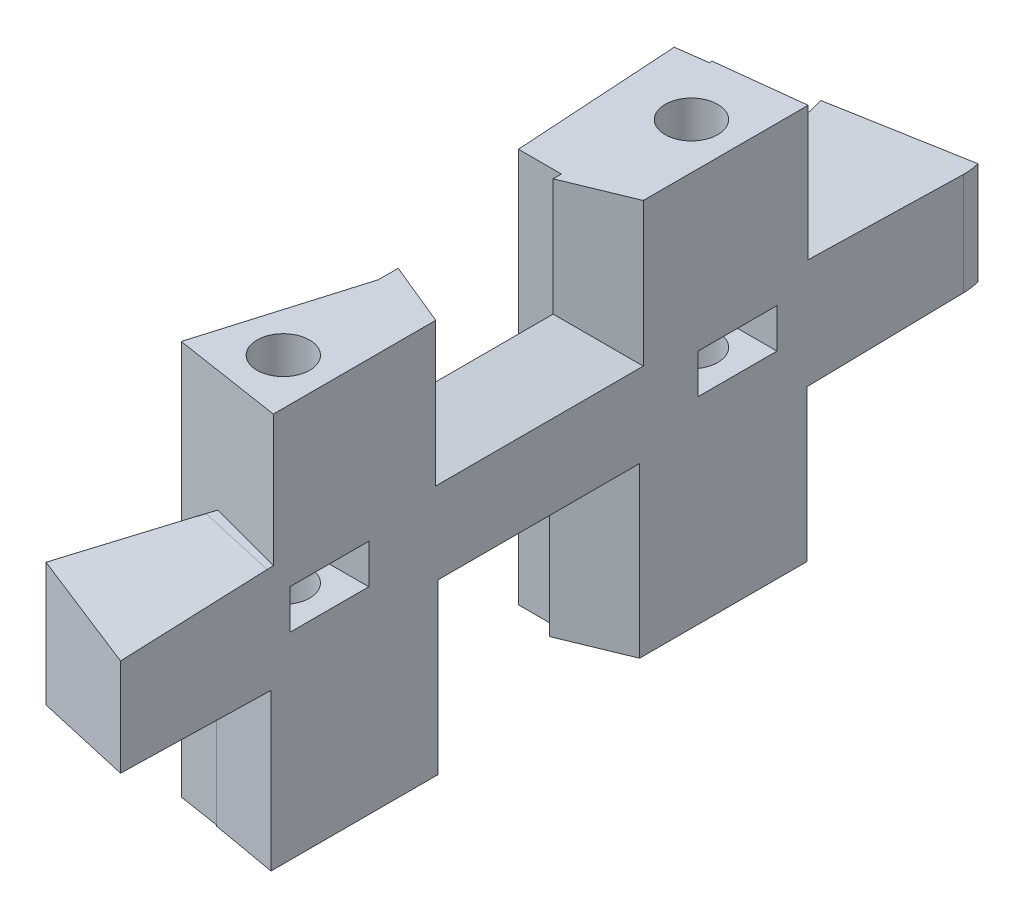
SolidWorks part; units mm, degrees
ref_plane "前视基准面" through (0, 0, 0) normal (0, 0, 1) x (1, 0, 0)
ref_plane "上视基准面" through (0, 0, 0) normal (0, 1, 0) x (1, 0, 0)
ref_plane "右视基准面" through (0, 0, 0) normal (1, 0, 0) x (0, 0, -1)
sketch "草图1" plane through (0, 0, 0) normal (0, 1, 0) x (1, 0, 0)
  line L0 (-7.1461, -29.9145) -> (11.328, -33.8659)
  line L1 (11.328, -33.8659) -> (15, -21.4825)
  line L2 (15, -21.4825) -> (3.725, -18.6661)
  line L3 (3.725, -18.6661) -> (7.1461, -7.129)
  line L4 (7.1461, -7.129) -> (15, -7.129)
  line L5 (15, -7.129) -> (15, 6.7954)
  line L6 (15, 6.7954) -> (3.8787, 6.7954)
  line L7 (3.8787, 6.7954) -> (3.0965, 19.265)
  line L8 (3.0965, 19.265) -> (14.551, 22.591)
  line L9 (14.551, 22.591) -> (11.328, 34.5234)
  line L10 (11.328, 34.5234) -> (-0.3541, 31.368)
  line L11 (-0.3541, 31.368) -> (-2.0104, 37.5)
  line L12 (-15, -37.5) -> (15, -37.5)
  line L13 (15, -37.5) -> (15, 37.5)
  line L14 (15, 37.5) -> (-15, 37.5)
  line L15 (-15, 37.5) -> (-15, -37.5)
sketch "草图2" plane through (0, 0, 0) normal (0, 1, 0) x (1, 0, 0)
  line L0 (15, -37.5) -> (15, 37.5) construction
  line L1 (-15, -37.5) -> (12, -37.5)
  line L2 (-15, -37.5) -> (-15, 37.5)
  line L3 (-15, 37.5) -> (12, 37.5)
  line L4 (12, -37.5) -> (12, 37.5)
  dimension "D1" = 3
extrude "凸台-拉伸1" add sketch "草图2" along normal blind 30
fillet "圆角1" radius 5 2 edges at (12, 15, 37.5) (12, 15, -37.5)
ref_plane "基准面1" through (18.6809, 0, -5.0055) normal (0.9659, 0, -0.2588) x (-0.2588, 0, -0.9659)
sketch "草图3" plane through (18.6809, 0, -5.0055) normal (0.9659, 0, -0.2588) x (-0.2588, 0, -0.9659)
  line L1 (18.233, 29.2901) -> (30.2366, 29.2901)
  line L2 (18.233, 29.2901) -> (18.233, 20.6669)
  line L3 (18.233, 20.6669) -> (30.2366, 20.6669)
  line L4 (30.2366, 29.2901) -> (30.2366, 20.6669)
  line L5 (17.9771, 10.856) -> (31.3653, 10.856)
  line L6 (17.9771, 10.856) -> (17.9771, 0)
  line L7 (17.9771, 0) -> (31.3653, 0)
  line L8 (31.3653, 10.856) -> (31.3653, 0)
extrude "切除-拉伸1" cut sketch "草图3" against normal through all and the other way blind 10
sketch "草图4" plane through (12, 0, 0) normal (1, 0, 0) x (0, 0, -1)
  line L1 (-5.6142, 29.5) -> (6.1635, 29.5)
  line L2 (-5.6142, 29.5) -> (-5.6142, 21.0937)
  line L3 (-5.6142, 21.0937) -> (6.1635, 21.0937)
  line L4 (6.1635, 29.5) -> (6.1635, 21.0937)
  line L5 (5.8858, -8.4868) -> (-5.445, -8.4868)
  line L6 (5.8858, -8.4868) -> (5.8858, 10.8216)
  line L7 (5.8858, 10.8216) -> (-5.445, 10.8216)
  line L8 (-5.445, -8.4868) -> (-5.445, 10.8216)
extrude "切除-拉伸2" cut sketch "草图4" against normal through all and the other way through all
ref_plane "基准面2" through (18.6809, 0, 5.0055) normal (0.9659, 0, 0.2588) x (0.2588, 0, -0.9659)
sketch "草图5" plane through (18.6809, 0, 5.0055) normal (0.9659, 0, 0.2588) x (0.2588, 0, -0.9659)
  line L1 (-17.946, 21.3139) -> (-28.4008, 21.3139)
  line L2 (-17.946, 21.3139) -> (-17.946, 29.231)
  line L3 (-17.946, 29.231) -> (-28.4008, 29.231)
  line L4 (-28.4008, 21.3139) -> (-28.4008, 29.231)
  line L5 (-17.946, -4.3786) -> (-28.1936, -4.3786)
  line L6 (-17.946, -4.3786) -> (-17.946, 10.297)
  line L7 (-17.946, 10.297) -> (-28.1936, 10.297)
  line L8 (-28.1936, -4.3786) -> (-28.1936, 10.297)
extrude "切除-拉伸3" cut sketch "草图5" against normal through all and the other way blind 10
sketch "草图6" plane through (0, 0, 0) normal (0, -1, 0) x (1, 0, 0)
  line L0 (7.1461, 7.129) -> (3.725, 18.6661)
  line L1 (3.725, 18.6661) -> (-0.0598, 31.4302)
  line L2 (-7.1461, 29.9145) -> (11.328, 33.8659) construction
  line L3 (-0.0598, 31.4302) -> (-15, 28.2346)
  line L4 (-15, 25.1689) -> (-15, 37.5) construction
  line L5 (-15, 28.2346) -> (-15, -49.9747)
  line L7 (-6.0272, -52.371) -> (-0.374, -31.203)
  line L8 (11.6182, -34.4163) -> (-15, -27.284) construction
  line L9 (-0.374, -31.203) -> (3.0965, -19.265)
  line L10 (3.0965, -19.265) -> (3.8787, -6.7954)
  line L11 (3.8787, -6.7954) -> (7.1461, -6.7954)
  line L12 (15, -6.7954) -> (3.8787, -6.7954) construction
  line L13 (7.1461, -6.7954) -> (7.1461, 7.129)
  line L14 (-0.3541, -31.368) -> (-2.0104, -37.5) construction
  line L15 (-6.0272, -52.371) -> (-15, -49.9747)
extrude "切除-拉伸4" cut sketch "草图6" against normal through all
sketch "草图7" plane through (18.6809, 0, -5.0055) normal (0.9659, 0, -0.2588) x (-0.2588, 0, -0.9659)
  line L0 (-34.4984, 30) -> (28.2868, 30) construction
  line L1 (16.233, 30) -> (32.2366, 30)
  line L2 (16.233, 30) -> (16.233, 18.6669)
  line L3 (16.233, 18.6669) -> (32.2366, 18.6669)
  line L4 (32.2366, 30) -> (32.2366, 18.6669)
  line L5 (18.233, 29.2901) -> (18.233, 20.6669) construction
  line L6 (30.2366, 29.2901) -> (30.2366, 20.6669) construction
  line L7 (18.233, 20.6669) -> (30.2366, 20.6669) construction
  dimension "D1" = 2
  dimension "D2" = 2
  dimension "D3" = 2
ref_plane "基准面3" through (8.0194, 0, -2.3314) normal (0.9602, 0, -0.2792) x (-0.2792, 0, -0.9602)
sketch "草图8" plane through (8.0194, 0, -2.3314) normal (0.9602, 0, -0.2792) x (-0.2792, 0, -0.9602)
  line L0 (30.067, 29.2901) -> (18.0607, 29.2901) construction
  line L1 (30.067, 29.2901) -> (30.067, 20.6669) construction
  line L2 (18.0607, 20.6669) -> (30.067, 20.6669) construction
  line L3 (18.0607, 29.2901) -> (18.0607, 20.6669) construction
  line L4 (30.067, 29.2901) -> (18.0607, 29.2901)
  line L5 (30.067, 29.2901) -> (30.067, 20.6669)
  line L6 (18.0607, 20.6669) -> (30.067, 20.6669)
  line L7 (18.0607, 29.2901) -> (18.0607, 20.6669)
ref_plane "基准面4" through (20.6127, 0, -5.5232) normal (0.9659, 0, -0.2588) x (-0.2588, 0, -0.9659)
sketch "草图9" plane through (20.6127, 0, -5.5232) normal (0.9659, 0, -0.2588) x (-0.2588, 0, -0.9659)
  line L1 (30.9943, 19.4228) -> (16.233, 19.4228)
  line L2 (30.9943, 19.4228) -> (30.9943, 30)
  line L3 (30.9943, 30) -> (16.233, 30)
  line L4 (16.233, 19.4228) -> (16.233, 30)
loft "切除-放样2" cut profiles "草图9", "草图8" connector at (12.5908, 30, -35.4614) connector at (-0.374, 29.2901, -31.203)
sketch "草图11" plane through (20.6127, 0, -5.5232) normal (0.9659, 0, -0.2588) x (-0.2588, 0, -0.9659)
  line L0 (36.7543, 0) -> (31.3653, 0) construction
  line L1 (16.233, 11.8398) -> (31.5532, 11.8398)
  line L2 (16.233, 11.8398) -> (16.233, 0)
  line L3 (16.233, 0) -> (31.5532, 0)
  line L4 (31.5532, 11.8398) -> (31.5532, 0)
sketch "草图12" plane through (8.0194, 0, -2.3314) normal (0.9602, 0, -0.2792) x (-0.2792, 0, -0.9602)
  line L0 (31.1954, 0) -> (31.1954, 10.856) construction
  line L1 (30.067, 10.856) -> (17.8047, 10.856) construction
  line L2 (17.8047, 10.856) -> (17.8047, 0) construction
  line L3 (31.1954, 0) -> (31.1954, 10.856)
  line L4 (30.067, 10.856) -> (17.8047, 10.856)
  line L5 (17.8047, 10.856) -> (17.8047, 0)
  line L6 (17.8047, 0) -> (31.1954, 0)
  line L7 (30.067, 10.856) -> (31.1954, 10.856)
loft "切除-放样4" cut profiles "草图12", "草图11" connector at (-0.689, 10.856, -32.2866) connector at (12.4462, 11.8398, -36.0012)
sketch "草图15" plane through (7.1461, 0, 0) normal (-1, 0, 0) x (0, 0, 1)
  line L0 (5.445, 0) -> (5.445, 10.8216) construction
  line L1 (-5.8858, 10.8216) -> (-5.8858, 0) construction
  line L2 (5.445, 10.8216) -> (-5.8858, 10.8216) construction
  line L3 (5.445, 0) -> (5.445, 10.8216)
  line L4 (-5.8858, 10.8216) -> (-5.8858, 0)
  line L5 (5.445, 10.8216) -> (-5.8858, 10.8216)
  line L6 (-5.8858, 0) -> (5.445, 0)
sketch "草图16" plane through (12, 0, 0) normal (1, 0, 0) x (0, 0, -1)
  line L0 (5.8858, 0) -> (20.6171, 0) construction
  line L1 (-7.445, 12.8216) -> (7.8858, 12.8216)
  line L2 (-7.445, 12.8216) -> (-7.445, 0)
  line L3 (-7.445, 0) -> (7.8858, 0)
  line L4 (7.8858, 12.8216) -> (7.8858, 0)
  line L5 (-5.445, 0) -> (-5.445, 10.8216) construction
  line L6 (-5.445, 10.8216) -> (5.8858, 10.8216) construction
  line L7 (5.8858, 10.8216) -> (5.8858, 0) construction
  dimension "D1" = 2
  dimension "D2" = 2
  dimension "D3" = 2
loft "切除-放样5" cut profiles "草图16", "草图15" connector at (12, 12.8216, 7.445) connector at (7.1461, 10.8216, 5.445)
sketch "草图17" plane through (7.1461, 0, 0) normal (-1, 0, 0) x (0, 0, 1)
  line L0 (5.6142, 29.5) -> (-6.1635, 29.5) construction
  line L1 (-6.1635, 29.5) -> (-6.1635, 21.0937) construction
  line L2 (-6.1635, 21.0937) -> (5.6142, 21.0937) construction
  line L3 (5.6142, 21.0937) -> (5.6142, 29.5) construction
  line L4 (5.6142, 29.5) -> (-6.1635, 29.5)
  line L5 (-6.1635, 29.5) -> (-6.1635, 21.0937)
  line L6 (-6.1635, 21.0937) -> (5.6142, 21.0937)
  line L7 (5.6142, 21.0937) -> (5.6142, 29.5)
sketch "草图18" plane through (12, 0, 0) normal (1, 0, 0) x (0, 0, -1)
  line L0 (-32.5, 30) -> (32.5, 30) construction
  line L1 (8.1635, 19.0937) -> (-7.6142, 19.0937)
  line L2 (8.1635, 19.0937) -> (8.1635, 30)
  line L3 (8.1635, 30) -> (-7.6142, 30)
  line L4 (-7.6142, 19.0937) -> (-7.6142, 30)
  line L5 (6.1635, 29.5) -> (6.1635, 21.0937) construction
  line L6 (6.1635, 21.0937) -> (-5.6142, 21.0937) construction
  line L7 (-5.6142, 21.0937) -> (-5.6142, 29.5) construction
  point P8 (6.1635, 25.2969)
  dimension "D1" = 2
  dimension "D2" = 2
  dimension "D3" = 2
loft "切除-放样6" cut profiles "草图18", "草图17" connector at (12, 19.0937, -8.1635) connector at (7.1461, 21.0937, -6.1635)
ref_plane "基准面6" through (20.6127, 0, 5.5232) normal (0.9659, 0, 0.2588) x (0.2588, 0, -0.9659)
sketch "草图19" plane through (20.6127, 0, 5.5232) normal (0.9659, 0, 0.2588) x (0.2588, 0, -0.9659)
  line L0 (-28.2868, 30) -> (-34.4105, 30) construction
  line L1 (-30.4008, 30) -> (-15.946, 30)
  line L2 (-30.4008, 30) -> (-30.4008, 19.3139)
  line L3 (-30.4008, 19.3139) -> (-15.946, 19.3139)
  line L4 (-15.946, 30) -> (-15.946, 19.3139)
  line L5 (-28.4008, 29.231) -> (-28.4008, 21.3139) construction
  line L6 (-17.946, 21.3139) -> (-17.946, 29.231) construction
  line L7 (-28.2868, 21.3139) -> (-17.946, 21.3139) construction
  dimension "D1" = 2
  dimension "D2" = 2
  dimension "D3" = 2
sketch "草图20" plane through (8.5116, 0, 2.5239) normal (-0.9587, 0, -0.2843) x (-0.2843, 0, 0.9587)
  line L0 (28.1757, 29.231) -> (28.1757, 21.3139) construction
  line L1 (17.7173, 29.231) -> (28.1757, 29.231) construction
  line L2 (17.7173, 21.3139) -> (17.7173, 29.231) construction
  line L3 (28.1757, 21.3139) -> (17.7173, 21.3139) construction
  line L4 (28.1757, 29.231) -> (28.1757, 21.3139)
  line L5 (17.7173, 29.231) -> (28.1757, 29.231)
  line L6 (17.7173, 21.3139) -> (17.7173, 29.231)
  line L7 (28.1757, 21.3139) -> (17.7173, 21.3139)
loft "切除-放样7" cut profiles "草图20", "草图19" connector at (3.4748, 29.231, 19.5102) connector at (16.4856, 30, 20.9258)
sketch "草图21" plane through (20.6127, 0, 5.5232) normal (0.9659, 0, 0.2588) x (0.2588, 0, -0.9659)
  line L0 (-17.946, 0) -> (-4.0855, 0) construction
  line L1 (-30.2868, 12.297) -> (-15.946, 12.297)
  line L2 (-30.2868, 12.297) -> (-30.2868, 0)
  line L3 (-30.2868, 0) -> (-15.946, 0)
  line L4 (-15.946, 12.297) -> (-15.946, 0)
  line L5 (-28.2868, 19.5169) -> (-28.2868, 0) construction
  line L6 (-17.946, 0) -> (-17.946, 10.297) construction
  line L7 (-17.946, 10.297) -> (-28.1936, 10.297) construction
  point P6 (-30.2868, 6.1485)
  dimension "D1" = 2
  dimension "D2" = 2
  dimension "D3" = 2
sketch "草图23" plane through (8.5116, 0, 2.5239) normal (-0.9587, 0, -0.2843) x (-0.2843, 0, 0.9587)
  line L7 (4.8033, 0) -> (17.7173, 0) construction
  line L8 (16.8524, 0) -> (28.7876, 0)
  line L9 (16.8524, 0) -> (16.8524, 11.1576)
  line L10 (16.8524, 11.1576) -> (28.7876, 11.1576)
  line L11 (28.7876, 0) -> (28.7876, 11.1576)
loft "切除-放样8" cut profiles "草图23", "草图21" connector at (3.7206, 0, 18.6809) connector at (16.4856, 0, 20.9258)
sketch "草图25" plane through (0, 30, 0) normal (0, 1, 0) x (1, 0, 0)
  line L0 (12, 20.701) -> (2.9776, 19.6741) construction
  line L1 (2.9776, 19.6741) -> (-0.374, 31.203) construction
  line L2 (-0.374, 31.203) -> (11.307, 35.0397) construction
  line L3 (12, 20.701) -> (12, 32.5) construction
  line L4 (0.5015, -29.537) -> (11.6254, -34.399)
  line L5 (3.4748, -19.5102) -> (0.5015, -29.537)
  line L6 (12, -20.4378) -> (3.4748, -19.5102)
  line L7 (12, -32.5) -> (12, -20.4378)
  line L8 (0.5015, -29.537) -> (11.6254, -34.399)
  line L9 (3.4748, -19.5102) -> (0.5015, -29.537)
  line L10 (12, -20.4378) -> (3.4748, -19.5102)
  line L11 (12, -32.5) -> (12, -20.4378)
  line L12 (7.1461, 6.1635) -> (12, 8.1635) construction
  line L13 (12, 8.1635) -> (12, -7.6142) construction
  line L14 (12, -7.6142) -> (7.1461, -5.6142) construction
  line L15 (7.1461, -5.6142) -> (7.1461, 6.1635) construction
  line L16 (12, 20.701) -> (2.9776, 19.6741)
  line L17 (2.9776, 19.6741) -> (-0.374, 31.203)
  line L18 (-0.374, 31.203) -> (11.307, 35.0397)
  line L19 (12, 20.701) -> (12, 32.5)
  line L20 (7.1461, 6.1635) -> (12, 8.1635)
  line L21 (12, 8.1635) -> (12, -7.6142)
  line L22 (12, -7.6142) -> (7.1461, -5.6142)
  line L23 (7.1461, -5.6142) -> (7.1461, 6.1635)
  arc A0 (12, 32.5) -> (11.307, 35.0397) centre (7, 32.5) ccw construction
  arc A1 (11.6254, -34.399) -> (12, -32.5) centre (7, -32.5) ccw
  arc A2 (11.6254, -34.399) -> (12, -32.5) centre (7, -32.5) ccw
  arc A3 (12, 32.5) -> (11.307, 35.0397) centre (7, 32.5) ccw
  dimension "D1" = 0
extrude "切除-拉伸5" cut sketch "草图25" against normal blind 1
sketch "草图26" plane through (12, 0, 0) normal (1, 0, 0) x (0, 0, -1)
  line L0 (-37.5, 0) -> (-37.5, 30) construction
  line L1 (-37.5, 3.2565) -> (-43.4233, 4.7171)
  line L2 (-43.4233, 4.7171) -> (-37.5, 28.1894)
  line L3 (37.5, 15.7229) -> (39.4095, 15.7229) construction
  arc A0 (-37.5, 3.2565) -> (-37.5, 28.1894) centre (-88.0576, 15.7229) ccw
extrude "切除-拉伸6" cut sketch "草图26" against normal through all and the other way through all
sketch "草图27" plane through (12, 0, 0) normal (1, 0, 0) x (0, 0, -1)
  line L0 (37.5, 15) -> (50037.5, 15) construction
  line L1 (37.5, 30) -> (37.5, 0) construction
  line L2 (37.5, 4.1538) -> (43.0606, 13.2108)
  line L3 (43.0606, 13.2108) -> (37.5, 25.8462)
  arc A0 (37.5, 4.1538) -> (37.5, 25.8462) centre (71.7679, 15) cw
  point P4 (37.5, 15)
extrude "切除-拉伸7" cut sketch "草图27" against normal through all and the other way through all contours L2 L3 A0
sketch "草图28" plane through (0, -4, 0) normal (0, -1, 0) x (1, 0, 0)
  circle A0 centre (-10.5, 33.4104) radius 2
  circle A1 centre (8.5, 15.7041) radius 2
  circle A2 centre (8.5, -15.3274) radius 2
extrude "切除-拉伸8" cut sketch "草图28" against normal through all
sketch "草图29" plane through (0, 30, 0) normal (0, 1, 0) x (1, 0, 0)
  line L0 (-0.0598, -31.4302) -> (-2.3142, -39.0326)
  line L1 (-2.3142, -39.0326) -> (-18.7698, -40.9424)
  line L2 (-18.7698, -40.9424) -> (-19.6531, -21.8617)
  line L3 (-19.6531, -21.8617) -> (-0.0598, -31.4302)
extrude "切除-拉伸9" cut sketch "草图29" against normal through all
sketch "草图30" plane through (12, 0, 0) normal (1, 0, 0) x (0, 0, -1)
  line L1 (-35.4082, -1.2051) -> (-45.4674, -1.2051)
  line L2 (-35.4082, -1.2051) -> (-35.4082, 36.6979)
  line L3 (-35.4082, 36.6979) -> (-45.4674, 36.6979)
  line L4 (-45.4674, -1.2051) -> (-45.4674, 36.6979)
  line L5 (35.7202, 32.6576) -> (51.21, 32.6576)
  line L6 (35.7202, 32.6576) -> (35.7202, -6.2451)
  line L7 (35.7202, -6.2451) -> (51.21, -6.2451)
  line L8 (51.21, 32.6576) -> (51.21, -6.2451)
extrude "切除-拉伸10" cut sketch "草图30" against normal through all
sketch "草图31" plane through (12, 0, 0) normal (1, 0, 0) x (0, 0, -1)
  line L1 (-34.2863, 0) -> (-43.0243, 0)
  line L2 (-34.2863, 0) -> (-34.2863, 34.7559)
  line L3 (-34.2863, 34.7559) -> (-43.0243, 34.7559)
  line L4 (-43.0243, 0) -> (-43.0243, 34.7559)
  line L5 (35.5758, 0) -> (46.5417, 0)
  line L6 (35.5758, 0) -> (35.5758, 34.7559)
  line L7 (35.5758, 34.7559) -> (46.5417, 34.7559)
  line L8 (46.5417, 0) -> (46.5417, 34.7559)
extrude "切除-拉伸11" cut sketch "草图31" against normal through all
sketch "草图32" plane through (8.5116, 0, 2.5239) normal (-0.9587, 0, -0.2843) x (-0.2843, 0, 0.9587)
  line L0 (33.1293, 0) -> (33.1293, 30) construction
  line L1 (28.1757, 30) -> (33.1293, 30) construction
  line L2 (28.7876, 0) -> (33.1293, 0) construction
  line L3 (33.1293, 28) -> (45.1179, 24.6253)
  line L4 (45.1179, 24.6253) -> (33.1293, 2)
  arc A0 (33.1293, 28) -> (33.1293, 2) centre (54.0896, 15) ccw
  dimension "D1" = 2
  dimension "D2" = 2
extrude "切除-拉伸12" cut sketch "草图32" against normal through all contours L3 L4 A0
sketch "草图33" plane through (7.4292, 0, -1.9841) normal (-0.9661, 0, 0.258) x (0.258, 0, 0.9661)
  line L0 (-34.7691, 30) -> (-34.7691, 0) construction
  line L1 (-34.7691, 0) -> (-31.548, 0) construction
  line L2 (-34.7691, 27) -> (-43.4252, 23.964)
  line L3 (-43.4252, 23.964) -> (-34.7691, 3)
  arc A0 (-34.7691, 27) -> (-34.7691, 3) centre (-54.2322, 15) cw
  dimension "D1" = 3
  dimension "D2" = 3
extrude "切除-拉伸13" cut sketch "草图33" against normal through all
sketch "草图35" plane through (8.0194, 0, -2.3314) normal (-0.9602, 0, 0.2792) x (0.2792, 0, 0.9602)
  line L9 (-59.3988, 44.3192) -> (-29.1319, 44.3192)
  line L10 (-59.3988, 44.3192) -> (-59.3988, -20.0993)
  line L11 (-59.3988, -20.0993) -> (-29.1319, -20.0993)
  line L12 (-29.1319, 44.3192) -> (-29.1319, -20.0993)
extrude "切除-拉伸14" cut sketch "草图35" against normal through all
sketch "草图36" plane through (8.5116, 0, 2.5239) normal (-0.9587, 0, -0.2843) x (-0.2843, 0, 0.9587)
  line L1 (26.8629, 0) -> (41.4454, 0)
  line L2 (26.8629, 0) -> (26.8629, 32.2072)
  line L3 (26.8629, 32.2072) -> (41.4454, 32.2072)
  line L4 (41.4454, 0) -> (41.4454, 32.2072)
extrude "切除-拉伸15" cut sketch "草图36" against normal through all
sketch "草图37" plane through (0, 0, 0) normal (0, -1, 0) x (1, 0, 0)
  line L0 (3.0491, -19.4282) -> (5.4632, -19.7489)
  line L1 (3.0491, -19.4282) -> (12, -20.6171) construction
  line L2 (5.4632, -19.7489) -> (2.5782, -31.0875)
  line L3 (-0.113, -30.3052) -> (11.8338, -33.7783) construction
  line L4 (2.5782, -31.0875) -> (0.8555, -35.943)
  line L5 (0.8555, -35.943) -> (-10.0486, -28.7441)
  line L6 (-10.0486, -28.7441) -> (3.0491, -19.4282)
extrude "切除-拉伸16" cut sketch "草图37" against normal through all
sketch "草图38" plane through (0, 30, 0) normal (0, 1, 0) x (1, 0, 0)
  line L0 (3.9435, -29.1884) -> (6.9971, -19.1887)
  line L1 (0.8747, -28.2784) -> (12, -31.5773) construction
  line L2 (6.9971, -19.1887) -> (3.7206, -18.6809)
  line L3 (3.7206, -18.6809) -> (-14.7956, -29.1884)
  line L4 (-14.7956, -29.1884) -> (3.9435, -29.1884)
extrude "切除-拉伸17" cut sketch "草图38" against normal through all
sketch "草图39" plane through (0, 30, 0) normal (0, 1, 0) x (1, 0, 0)
  line L0 (6.9971, -19.1887) -> (12, -19.964)
  line L1 (12, -20.4378) -> (12, -7.6142) construction
  line L2 (12, -19.964) -> (12, -21.2466)
  line L3 (12, -31.5773) -> (12, -20.4378) construction
  line L4 (12, -21.2466) -> (6.6231, -20.4133)
  line L5 (6.9773, -19.2537) -> (3.9435, -29.1884) construction
  line L6 (6.6231, -20.4133) -> (6.9971, -19.1887)
extrude "切除-拉伸19" cut sketch "草图39" against normal blind 9.2
sketch "草图40" plane through (-2.0574, 0, 18.9082) normal (-0.1082, 0, 0.9941) x (0.9941, 0, 0.1082)
  line L3 (14.1403, 20.8) -> (8.9274, 20.8)
  line L4 (8.9274, 20.8) -> (14.1403, 20.0034)
  line L5 (14.1403, 20.0034) -> (14.1403, 20.8)
  line L6 (14.1403, 20.8) -> (8.9274, 20.8)
  line L7 (8.9274, 20.8) -> (14.1403, 20.0034)
  line L8 (14.1403, 20.0034) -> (14.1403, 20.8)
  dimension "D1" = 0
extrude "切除-拉伸20" cut sketch "草图40" against normal up to surface (0.7053 mm away) up to face at (7.2995, 19.4333, 19.2356)
sketch "草图41" plane through (0, 0, 0) normal (1, 0, 0) x (0, 0, -1)
  line L0 (-13.7041, 15) -> (-12.7041, 15)
  line L1 (-13.7041, 0) -> (-13.7041, 30) construction
  line L2 (-12.7041, 15) -> (-12.7041, 18)
  line L3 (-12.7041, 18) -> (-18.6809, 18)
  line L4 (-18.6809, 18) -> (-18.6809, 15)
  line L5 (-18.6809, 15) -> (-13.7041, 15)
  line L6 (12.3274, 15) -> (18.3274, 15)
  line L7 (18.3274, 15) -> (18.3274, 18)
  line L8 (18.3274, 18) -> (12.3274, 18)
  line L9 (12.3274, 18) -> (12.3274, 15)
  line L10 (-18.6809, 30) -> (-18.6809, 0) construction
  line L11 (13.3274, 30) -> (13.3274, 0) construction
  line L12 (17.3274, 0) -> (17.3274, 30) construction
  dimension "D1" = 1
  dimension "D2" = 3
  dimension "D3" = 0
  dimension "D4" = 1
  dimension "D5" = 1
extrude "切除-拉伸21" cut sketch "草图41" along normal up to surface (12 mm away) up to face at (12, 15.7182, 1.9276)
